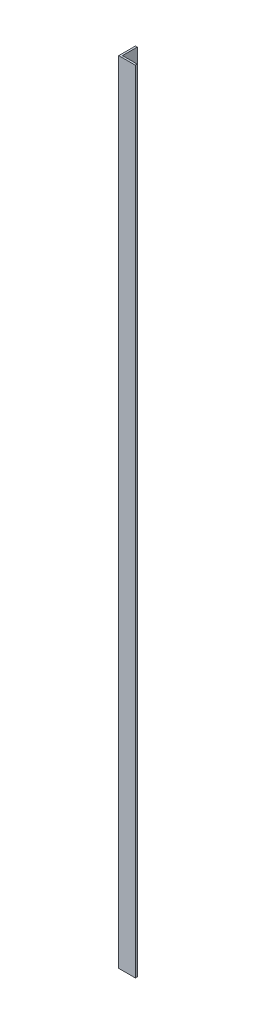
SolidWorks part; units mm, degrees
ref_plane "Front Plane" through (0, 0, 0) normal (0, 0, 1) x (1, 0, 0)
ref_plane "Top Plane" through (0, 0, 0) normal (0, 1, 0) x (1, 0, 0)
ref_plane "Right Plane" through (0, 0, 0) normal (1, 0, 0) x (0, 0, -1)
sketch "Sketch1" plane through (0, 0, 0) normal (0, 1, 0) x (1, 0, 0)
  line L0 (0, 0) -> (0, -19.05)
  line L1 (0, -19.05) -> (19.05, -19.05)
  line L2 (0, 0) -> (2.15, 0)
  line L3 (19.05, -19.05) -> (19.05, -16.9)
  line L4 (19.05, -16.9) -> (2.15, -16.9)
  line L5 (2.15, -16.9) -> (2.15, 0)
  dimension "D1" = 19.05
  dimension "D2" = 19.05
  dimension "D4" = 2.15
extrude "Boss-Extrude1" add sketch "Sketch1" along normal blind 904.4
